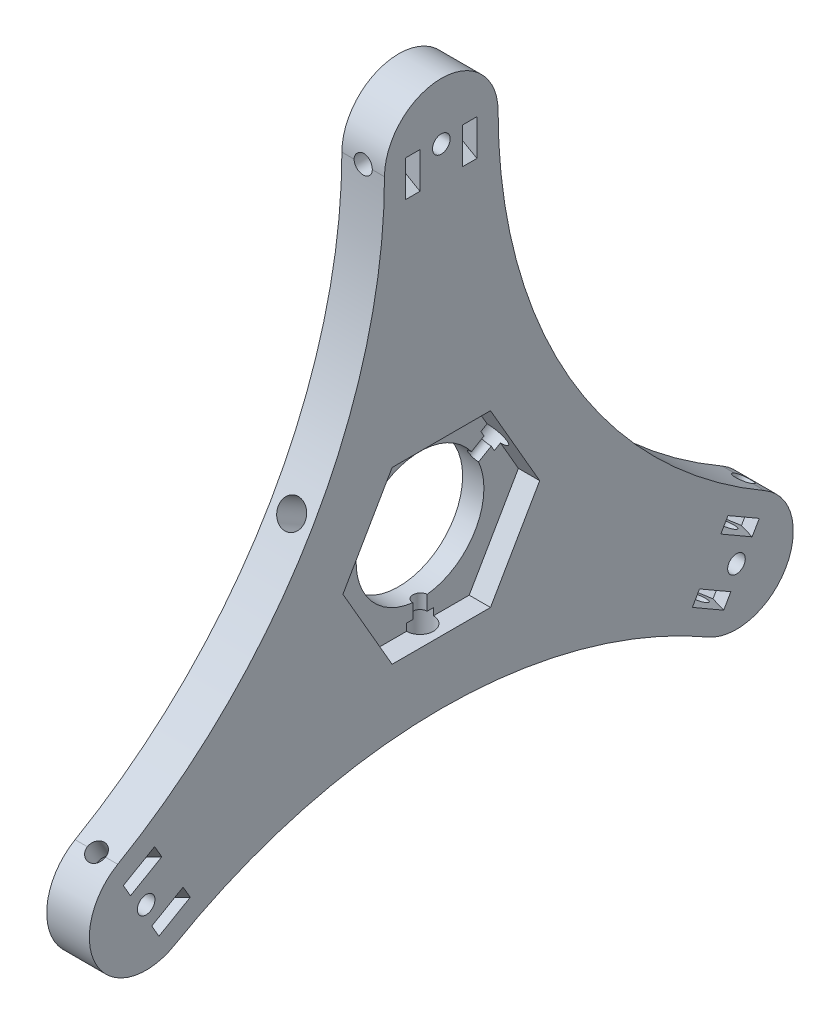
SolidWorks part; units mm, degrees
ref_plane "Front Plane" through (0, 0, 0) normal (0, 0, 1) x (1, 0, 0)
ref_plane "Top Plane" through (0, 0, 0) normal (0, 1, 0) x (1, 0, 0)
ref_plane "Right Plane" through (0, 0, 0) normal (1, 0, 0) x (0, 0, -1)
sketch "Sketch1" plane through (0, 0, 0) normal (1, 0, 0) x (0, 0, -1)
  line L0 (0, 0) -> (0, 76.2) construction
  line L1 (0, 0) -> (65.9911, -38.1) construction
  line L2 (0, 0) -> (-65.9911, -38.1) construction
  line L3 (-65.9911, -38.1) -> (0, 76.2) construction
  line L4 (0, 76.2) -> (65.9911, -38.1) construction
  line L5 (65.9911, -38.1) -> (-65.9911, -38.1) construction
  line L6 (-12.7, 76.2) -> (12.7, 76.2) construction
  line L8 (-3.6662, 6.35) -> (-7.3323, 0)
  line L9 (-7.3323, 0) -> (-3.6662, -6.35)
  line L10 (-3.6662, -6.35) -> (3.6662, -6.35)
  line L11 (3.6662, -6.35) -> (7.3323, 0)
  line L12 (7.3323, 0) -> (3.6662, 6.35)
  line L13 (3.6662, 6.35) -> (-3.6662, 6.35)
  circle A1 centre (0, 76.2) radius 1.9685
  circle A2 centre (65.9911, -38.1) radius 1.9685
  circle A3 centre (-65.9911, -38.1) radius 1.9685
  arc A4 (12.7, 76.2) -> (-12.7, 76.2) centre (0, 76.2) ccw
  arc A5 (59.6411, -49.0985) -> (72.3411, -27.1015) centre (65.9911, -38.1) ccw
  arc A6 (-72.3411, -27.1015) -> (-59.6411, -49.0985) centre (-65.9911, -38.1) ccw
  arc A7 (-12.7, 76.2) -> (-72.3411, -27.1015) centre (-131.9823, 76.2) cw
  arc A8 (12.7, 76.2) -> (72.3411, -27.1015) centre (131.9823, 76.2) ccw
  arc A9 (-59.6411, -49.0985) -> (59.6411, -49.0985) centre (0, -152.4) cw
  circle A10 centre (0, 0) radius 6.35 construction
  dimension "D1" = 12.7
  dimension "D2" = 3.937
  dimension "D4" = 25.4
  dimension "D3" = 76.2
extrude "Boss-Extrude1" add sketch "Sketch1" along normal blind 9.525 contours A6 A9 A5 A8 A4 A7 A1 A2 A3 region at (0, 15.5067, -26.8583)
sketch "Sketch3" plane through (0, 3.175, 5.4993) normal (0, -0.5, -0.866) x (-1, 0, 0)
  line L0 (-9.525, 0) -> (0, 0) construction
  line L4 (0, -3.6662) -> (0, 3.6662)
  line L5 (0, 3.6662) -> (-9.525, 3.6662)
  line L6 (-9.525, 3.6662) -> (-9.525, -3.6662)
  line L7 (-9.525, -3.6662) -> (0, -3.6662)
  line L8 (0, -3.6662) -> (0, 3.6662) construction
  line L9 (0, 3.6662) -> (-9.525, 3.6662) construction
  line L10 (-9.525, 3.6662) -> (-9.525, -3.6662) construction
  line L11 (-9.525, -3.6662) -> (0, -3.6662) construction
  circle A0 centre (-4.7625, 0) radius 1.6
  dimension "D2" = 3.2
  dimension "D1" = 0
extrude "Cut-Extrude1" cut sketch "Sketch3" against normal through all
sketch "Sketch5" plane through (0, 3.175, 5.4993) normal (0, -0.5, -0.866) x (-1, 0, 0)
  circle A0 centre (-4.7625, 0) radius 3
  dimension "D1" = 6
extrude "Cut-Extrude3" cut sketch "Sketch5" against normal through all from offset 11.1125 offset against normal yes
ref_axis "Axis1" through (-0.4763, 0, 0) along (1, 0, 0)
pattern_circular "CirPattern9" count 3 over 360 about axis through (-0.4763, 0, 0) along (1, 0, 0) of "Cut-Extrude3", "Cut-Extrude1"
sketch "Sketch4" plane through (0, 3.175, 5.4993) normal (0, -0.5, -0.866) x (-1, 0, 0)
  line L0 (-9.525, 0) -> (0, 0) construction
  line L1 (-3.1748, 2.75) -> (-6.3502, 2.75)
  line L2 (-6.3502, 2.75) -> (-7.9379, 0) construction
  line L3 (-7.9379, 0) -> (-6.3502, -2.75) construction
  line L4 (-6.3502, -2.75) -> (-3.1748, -2.75)
  line L5 (-3.1748, -2.75) -> (-1.5871, 0)
  line L6 (-1.5871, 0) -> (-3.1748, 2.75)
  line L7 (-6.3502, 2.75) -> (-9.525, 2.75)
  line L8 (-9.525, 3.6662) -> (-9.525, -3.6662) construction
  line L9 (-9.525, 2.75) -> (-9.525, -2.75)
  line L10 (-9.525, -2.75) -> (-6.3502, -2.75)
  circle A0 centre (-4.7625, 0) radius 2.75 construction
  dimension "D1" = 5.5
extrude "Cut-Extrude2" cut sketch "Sketch4" against normal blind 3.2 from offset 3.175 offset against normal yes
sketch "Sketch6" plane through (0, 0, 0) normal (0, 0, 1) x (1, 0, 0)
  line L0 (9.525, 76.2) -> (0, 76.2) construction
  line L1 (9.525, 74.2315) -> (9.525, 78.1685) construction
  line L2 (9.525, 74.2315) -> (9.525, 78.1685) construction
  line L3 (4.7625, 88.9) -> (4.7625, 71.7991) construction
  line L4 (9.525, 88.9) -> (0, 88.9) construction
  circle A0 centre (4.7625, 76.2) radius 2.032
  dimension "D1" = 4.064
extrude "Cut-Extrude4" cut sketch "Sketch6" against normal through all
sketch "Sketch7" plane through (0, 0, 0) normal (0, 0, 1) x (1, 0, 0)
  line L0 (8.2625, 78.2207) -> (9.525, 77.4918)
  line L1 (1.2625, 74.1793) -> (4.7625, 72.1585)
  line L2 (4.7625, 72.1585) -> (8.2625, 74.1793) construction
  line L3 (8.2625, 74.1793) -> (8.2625, 78.2207) construction
  line L4 (8.2625, 78.2207) -> (4.7625, 80.2415)
  line L5 (4.7625, 80.2415) -> (1.2625, 78.2207)
  line L6 (1.2625, 78.2207) -> (1.2625, 74.1793)
  line L7 (9.525, 74.2315) -> (9.525, 78.1685) construction
  line L8 (9.525, 77.4918) -> (9.525, 69.4089)
  line L9 (9.525, -27.1015) -> (9.525, 76.2) construction
  line L10 (4.7625, 72.1585) -> (9.525, 69.4089)
  circle A0 centre (4.7625, 76.2) radius 3.5 construction
  dimension "D1" = 7
extrude "Cut-Extrude5" cut sketch "Sketch7" against normal blind 3.2 from offset 4.7625 offset against normal yes
mirror "Mirror1" about plane through (0, 0, 0) normal (0, 0, 1) of "Cut-Extrude5", "Cut-Extrude4"
pattern_circular "CirPattern1" count 3 over 360 about axis through (-0.4763, 0, 0) along (1, 0, 0) of "Cut-Extrude5", "Mirror1"
sketch "Sketch8" plane through (9.525, 0, 0) normal (1, 0, 0) x (0, 0, -1)
  circle A0 centre (0, 0) radius 14.2875
  dimension "D1" = 28.575
extrude "Cut-Extrude6" cut sketch "Sketch8" against normal through all
sketch "Sketch9" plane through (9.525, 0, 0) normal (1, 0, 0) x (0, 0, -1)
  line L1 (-10.9985, 19.05) -> (-21.997, 0)
  line L2 (-21.997, 0) -> (-10.9985, -19.05)
  line L3 (-10.9985, -19.05) -> (10.9985, -19.05)
  line L4 (10.9985, -19.05) -> (21.997, 0)
  line L5 (21.997, 0) -> (10.9985, 19.05)
  line L6 (10.9985, 19.05) -> (-10.9985, 19.05)
  circle A0 centre (0, 0) radius 19.05 construction
  dimension "D1" = 38.1
extrude "Cut-Extrude7" cut sketch "Sketch9" against normal blind 4.7625
